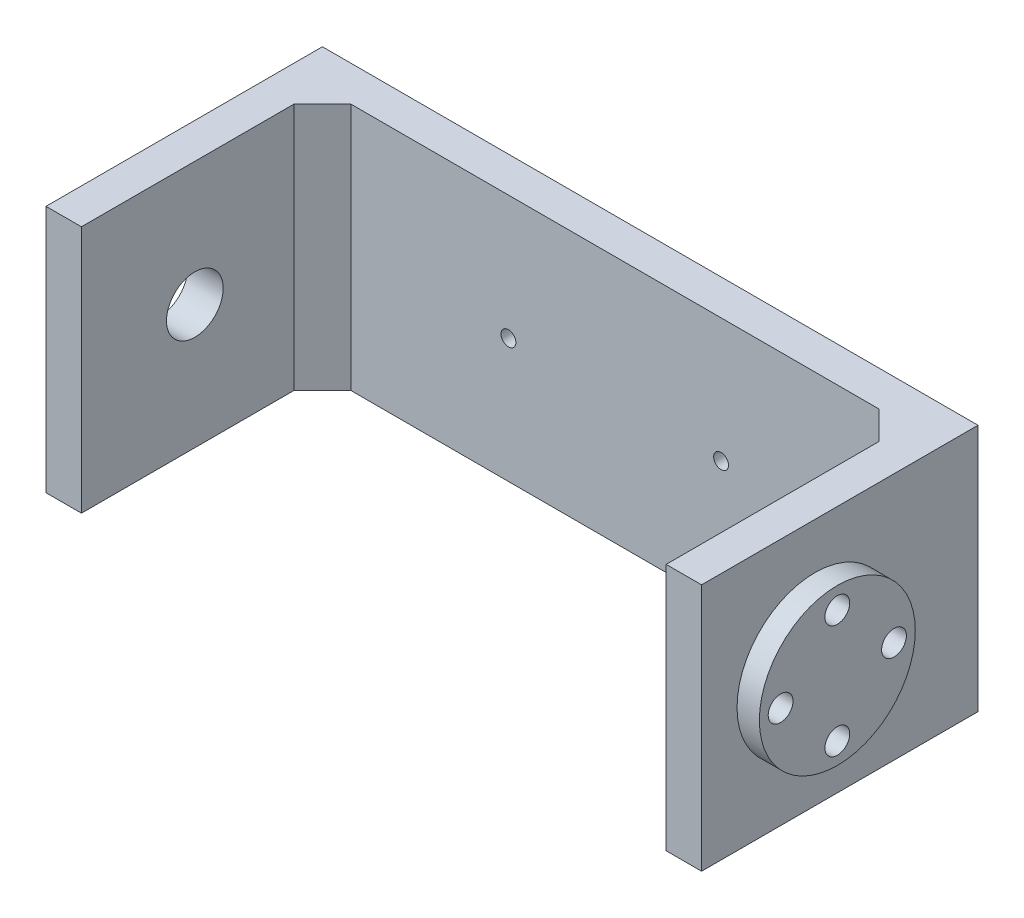
SolidWorks part; units mm, degrees
ref_plane "Front Plane" through (0, 0, 0) normal (0, 0, 1) x (1, 0, 0)
ref_plane "Top Plane" through (0, 0, 0) normal (0, 1, 0) x (1, 0, 0)
ref_plane "Right Plane" through (0, 0, 0) normal (1, 0, 0) x (0, 0, -1)
sketch "Sketch1" plane through (0, 0, 0) normal (0, 1, 0) x (1, 0, 0)
  line L0 (0, 0) -> (0, 39)
  line L1 (0, 39) -> (92.5, 39)
  line L2 (92.5, 39) -> (92.5, 0)
  line L3 (92.5, 0) -> (87.5, 0)
  line L4 (87.5, 0) -> (87.5, 34)
  line L5 (87.5, 34) -> (5, 34)
  line L6 (5, 34) -> (5, 0)
  line L7 (5, 0) -> (0, 0)
  dimension "D1" = 82.5
  dimension "D2" = 5
  dimension "D3" = 5
  dimension "D4" = 39
  dimension "D5" = 34
  dimension "D6" = 39
extrude "Boss-Extrude2" add sketch "Sketch1" along normal blind 35
sketch "Sketch3" plane through (92.5, 0, 0) normal (1, 0, 0) x (0, 0, -1)
  line L2 (16, 6.5) -> (16, 9.5)
  line L6 (0, 0) -> (39, 0)
  line L7 (39, 0) -> (39, 35)
  line L8 (39, 35) -> (0, 35)
  line L9 (0, 35) -> (0, 0)
  line L10 (0, 0) -> (39, 0)
  line L11 (39, 0) -> (39, 35)
  line L12 (39, 35) -> (0, 35)
  line L13 (0, 35) -> (0, 0)
  circle A0 centre (16, 17.5) radius 11
  circle A1 centre (16, 9.5) radius 1.75
  circle A2 centre (8, 17.5) radius 1.75
  circle A3 centre (16, 25.5) radius 1.75
  circle A4 centre (24, 17.5) radius 1.75
  point P17 (16, 17.5)
  dimension "D2" = 22
  dimension "D4" = 3.5
  dimension "D1" = 0
  dimension "D3" = 3
  dimension "D5" = 4
extrude "Boss-Extrude5" add sketch "Sketch3" along normal blind 3.15 contours A1 A0 A4 A3 A2 region at (92.5, 17.5, -16)
sketch "Sketch5" plane through (92.5, 0, 0) normal (1, 0, 0) x (0, 0, -1)
  circle A0 centre (16, 9.5) radius 1.75 construction
  circle A1 centre (24, 17.5) radius 1.75 construction
  circle A2 centre (16, 25.5) radius 1.75 construction
  circle A3 centre (8, 17.5) radius 1.75 construction
  circle A4 centre (16, 9.5) radius 1.75
  circle A5 centre (24, 17.5) radius 1.75
  circle A6 centre (16, 25.5) radius 1.75
  circle A7 centre (8, 17.5) radius 1.75
extrude "Cut-Extrude2" cut sketch "Sketch5" against normal up to next
sketch "Sketch6" plane through (87.5, 0, 0) normal (-1, 0, 0) x (0, 0, 1)
  circle A0 centre (-16, 9.5) radius 2.5
  circle A1 centre (-24, 17.5) radius 2.5
  circle A2 centre (-16, 25.5) radius 2.5
  circle A3 centre (-8, 17.5) radius 2.5
  dimension "D1" = 5
  dimension "D2" = 5
  dimension "D3" = 5
  dimension "D4" = 5
extrude "Cut-Extrude3" cut sketch "Sketch6" against normal blind 2.15
sketch "Sketch7" plane through (0, 0, 0) normal (-1, 0, 0) x (0, 0, 1)
  circle A0 centre (-16, 17.5) radius 4
  dimension "D2" = 8
extrude "Cut-Extrude4" cut sketch "Sketch7" against normal up to next
chamfer "Chamfer1" distance 4 angle 45 2 edges at (5, 17.5, -34) (87.5, 17.5, -34)
sketch "Sketch8" plane through (0, 0, -39) normal (0, 0, -1) x (-1, 0, 0)
  line L0 (-46.25, 17.5) -> (-61.25, 17.5)
  line L3 (-46.25, 0) -> (-46.25, 35)
  line L4 (-92.5, 0) -> (0, 0) construction
  line L5 (-92.5, 35) -> (0, 35) construction
  line L6 (-29.25, 16.3453) -> (-31.25, 15.1906)
  line L7 (-61.25, 19.8094) -> (-63.25, 18.6547)
  line L8 (-63.25, 18.6547) -> (-63.25, 16.3453)
  line L9 (-63.25, 16.3453) -> (-61.25, 15.1906)
  line L10 (-61.25, 15.1906) -> (-59.25, 16.3453)
  line L11 (-59.25, 16.3453) -> (-59.25, 18.6547)
  line L12 (-59.25, 18.6547) -> (-61.25, 19.8094)
  line L13 (-29.25, 18.6547) -> (-29.25, 16.3453)
  line L14 (-31.25, 19.8094) -> (-29.25, 18.6547)
  line L15 (-33.25, 18.6547) -> (-31.25, 19.8094)
  line L16 (-33.25, 16.3453) -> (-33.25, 18.6547)
  line L17 (-31.25, 15.1906) -> (-33.25, 16.3453)
  circle A0 centre (-61.25, 17.5) radius 2 construction
  circle A1 centre (-31.25, 17.5) radius 2 construction
  circle A2 centre (-61.25, 17.5) radius 1.05
  circle A3 centre (-31.25, 17.5) radius 1.05
  dimension "D2" = 4
  dimension "D3" = 2.1
  dimension "D4" = 2.1
  dimension "D1" = 15
extrude "Cut-Extrude5" cut sketch "Sketch8" against normal blind 2 contours L11 L12 L7 L8 L9 L10 | L17 L6 L13 L14 L15 L16 region at (59.3111, 16.9226, -39) region at (30.2806, 15.8209, -39)
sketch "Sketch9" plane through (0, 0, -39) normal (0, 0, -1) x (-1, 0, 0)
  circle A0 centre (-61.25, 17.5) radius 1.05 construction
  circle A1 centre (-31.25, 17.5) radius 1.05 construction
  circle A2 centre (-61.25, 17.5) radius 1.05
  circle A3 centre (-31.25, 17.5) radius 1.05
extrude "Cut-Extrude6" cut sketch "Sketch9" against normal up to next
